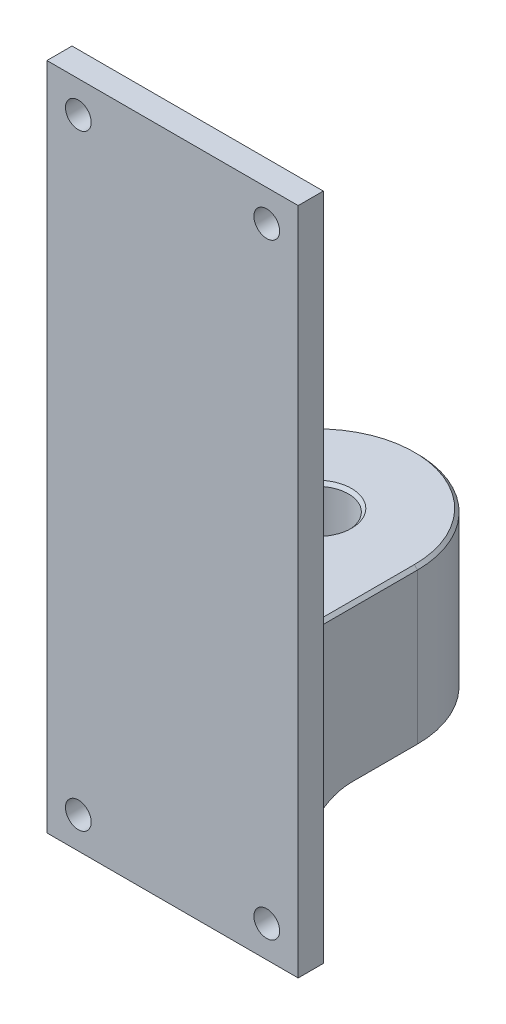
SolidWorks part; units mm, degrees
material "6061 Alloy"
ref_plane "Front Plane" through (0, 0, 0) normal (0, 0, 1) x (1, 0, 0)
ref_plane "Top Plane" through (0, 0, 0) normal (0, 1, 0) x (1, 0, 0)
ref_plane "Right Plane" through (0, 0, 0) normal (1, 0, 0) x (0, 0, -1)
sketch "Sketch1" plane through (0, 0, 0) normal (0, 0, 1) x (1, 0, 0)
  line L1 (40, -106.5) -> (-40, -106.5)
  line L2 (40, -106.5) -> (40, 106.5)
  line L3 (40, 106.5) -> (-40, 106.5)
  line L4 (-40, -106.5) -> (-40, 106.5)
  line L5 (40, -106.5) -> (-40, 106.5) construction
  line L6 (40, 106.5) -> (-40, -106.5) construction
  point P0 (0, 0)
  dimension "D1" = 213
  dimension "D2" = 80
extrude "Boss-Extrude1" add sketch "Sketch1" along normal blind 10
sketch "Sketch2" plane through (0, 0, 0) normal (0, 1, 0) x (1, 0, 0)
  line L0 (40, 0) -> (-40, 0) construction
  line L1 (-32, 36) -> (-32, 0)
  line L2 (32, 36) -> (32, 0)
  line L3 (-32, 0) -> (32, 0)
  line L4 (-1014.7316, 68) -> (48985.2684, 68) construction
  line L5 (40, -10) -> (-40, -10) construction
  arc A0 (32, 36) -> (-32, 36) centre (0, 36) ccw
  dimension "D1" = 64
  dimension "D2" = 78
extrude "Boss-Extrude2" add sketch "Sketch2" against normal blind 50 from offset 20 offset against normal yes
fillet "Fillet1" radius 15 1 edges at (0, -70, 0)
sketch "Sketch3" plane through (0, -20, 0) normal (0, 1, 0) x (1, 0, 0)
  circle A0 centre (0, 36) radius 10
  dimension "D1" = 20
extrude "Cut-Extrude1" cut sketch "Sketch3" against normal through all
chamfer "Chamfer1" distance 1 angle 45 8 edges at (-32, -20, -18) (0, -20, -68) (32, -20, -18) (-32, -74.3934, -4.3934) (-32, -70, -25.5) (0, -70, -68) (32, -70, -25.5) (32, -74.3934, -4.3934) tangent propagation no
hole_wizard "Ø8.2 (8.2) Diameter Hole1" positions "Sketch4" profile "Sketch5" hole size "Ø8.2" standard "ANSI Metric" end condition through all
sketch "Sketch4" plane through (0, 0, 0) normal (0, 0, -1) x (-1, 0, 0)
  line L1 (-30, 96.5) -> (30, 96.5) construction
  line L2 (-30, 96.5) -> (-30, -96.5) construction
  line L3 (-30, -96.5) -> (30, -96.5) construction
  line L4 (30, 96.5) -> (30, -96.5) construction
  line L5 (-30, 96.5) -> (30, -96.5) construction
  line L6 (-30, -96.5) -> (30, 96.5) construction
  line L7 (-40, 106.5) -> (40, 106.5) construction
  line L8 (-40, -106.5) -> (-40, 106.5) construction
  line L9 (40, 106.5) -> (40, -106.5) construction
  line L10 (40, -106.5) -> (-40, -106.5) construction
  point P2 (30, -96.5)
  point P85 (-30, 96.5)
  point P86 (-30, -96.5)
  point P87 (30, 96.5)
  dimension "D1" = 10
  dimension "D2" = 10
  dimension "D3" = 10
  dimension "D4" = 10
sketch "Sketch5" plane through (-30, -96.5, 0) normal (1, 0, 0) x (0, 1, 0)
  line L0 (0, 0) -> (0, 10)
  line L1 (0, 10) -> (4.1, 10)
  line L2 (4.1, 10) -> (4.1, 0)
  line L5 (4.1, 0) -> (0, 0)
  line L11 (0, -6.35) -> (0, 107.95) construction
  dimension "Thru Hole Dia." = 8.2
  dimension "Thru Hole Depth" = 10
chamfer "Chamfer2" distance 2 angle 45 4 edges at (0, 106.5, 0) (-40, 0, 0) (0, -106.5, 0) (40, 0, 0)
chamfer "Chamfer3" distance 1 angle 45 6 edges at (0, -70, -26) (0, -20, -26) (-34.1, -96.5, 0) (25.9, -96.5, 0) (-34.1, 96.5, 0) (25.9, 96.5, 0)
fillet "Fillet2" radius 1 5 edges at (-32, -50.2161, 0) (-31.5, -20.5, 0) (0, -20, 0) (31.5, -20.5, 0) (32, -50.2161, 0)
